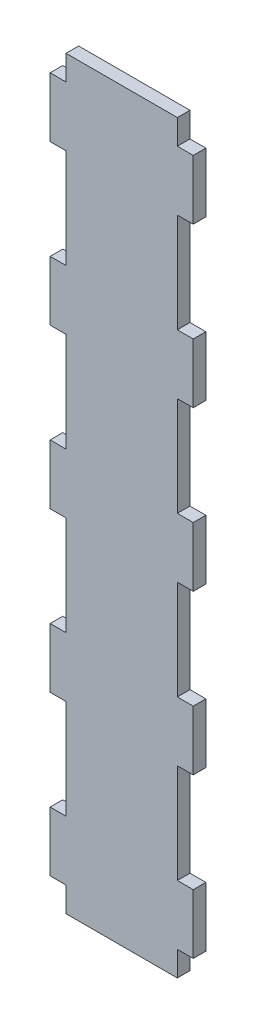
SolidWorks part; units mm, degrees
note: The reader was unsure of these and kept them because the rebuilt part matched: thickness of "Base-Flange1", "Sheet-Metal1", "Sheet-Metal2", "Sheet-Metal3", "Sheet-Metal4".
material "Acrylic (Medium-high impact)"
ref_plane "Front Plane" through (0, 0, 0) normal (0, 0, 1) x (1, 0, 0)
ref_plane "Top Plane" through (0, 0, 0) normal (0, 1, 0) x (1, 0, 0)
ref_plane "Right Plane" through (0, 0, 0) normal (1, 0, 0) x (0, 0, -1)
sketch "Sketch1" plane through (0, 0, 0) normal (0, 0, 1) x (1, 0, 0)
  line L1 (7.0811, 110.7088) -> (43.0811, 110.7088)
  line L2 (7.0811, 110.7088) -> (7.0811, -89.2912)
  line L3 (7.0811, -89.2912) -> (43.0811, -89.2912)
  line L4 (43.0811, 110.7088) -> (43.0811, -89.2912)
  dimension "D1" = 36
  dimension "D2" = 200
base flange "Base-Flange1" sketch "Sketch1" thickness 3.175 reverse thickness direction no parameters "D1"=0.7366
sketch "Sketch2" plane through (0, 0, 0) normal (0, 0, 1) x (1, 0, 0)
  line L0 (7.0811, 110.7088) -> (7.0811, -89.2912) construction
  line L1 (7.0811, -101.7912) -> (11.0811, -101.7912)
  line L2 (7.0811, -101.7912) -> (7.0811, -76.7912)
  line L3 (7.0811, -76.7912) -> (11.0811, -76.7912)
  line L4 (11.0811, -101.7912) -> (11.0811, -76.7912)
  line L6 (25.0811, -89.2912) -> (25.0811, -51.7912) construction
  line L7 (39.0811, -101.7912) -> (39.0811, -76.7912)
  line L8 (43.0811, -76.7912) -> (39.0811, -76.7912)
  line L9 (43.0811, -101.7912) -> (43.0811, -76.7912)
  line L10 (43.0811, -101.7912) -> (39.0811, -101.7912)
  line L11 (7.0811, -89.2912) -> (43.0811, -89.2912) construction
  dimension "D1" = 4
  dimension "D2" = 25
  dimension "D3" = 12.5
extrude "Cut-Extrude1" cut sketch "Sketch2" against normal blind 10
pattern_linear "LPattern1" count 6 spacing 40 along (0, 1, 0) of "Cut-Extrude1"
sketch "Sketch3" plane through (0, 0, 0) normal (0, 0, 1) x (1, 0, 0)
  line L0 (11.0811, 98.2088) -> (11.0811, 110.7088) construction
  line L1 (11.0811, 104.4588) -> (39.0811, 104.4588)
  line L2 (11.0811, 104.4588) -> (11.0811, 110.7088)
  line L3 (11.0811, 110.7088) -> (39.0811, 110.7088)
  line L4 (39.0811, 104.4588) -> (39.0811, 110.7088)
  line L5 (11.0811, -76.7912) -> (11.0811, -89.2912) construction
  line L6 (11.0811, -83.0412) -> (39.0811, -83.0412)
  line L7 (11.0811, -83.0412) -> (11.0811, -89.2912)
  line L8 (11.0811, -89.2912) -> (39.0811, -89.2912)
  line L9 (39.0811, -83.0412) -> (39.0811, -89.2912)
extrude "Cut-Extrude2" cut sketch "Sketch3" against normal blind 10
sketch "Bend-Lines1" [suppressed] plane through (0, 0, 0) normal (0, 1, 0) x (1, 0, 0)
sketch "Bounding-Box1" [suppressed] plane through (0, 0, 0) normal (0, 1, 0) x (1, 0, 0)
sheet metal parameters "Sheet-Metal1" thickness 3.175 parameters "D1"=0.7366, "D7"=0.7366
flat pattern "Flat-Pattern1" [suppressed]
sketch "Bend-Lines2" plane through (0, 0, 0) normal (0, 1, 0) x (1, 0, 0)
sketch3d "Bounding-Box2" [suppressed]
  line L0 (44.2561, 110.7088, 0) -> (44.2561, -89.2912, 0) construction
  line L1 (4.2561, 110.7088, 0) -> (4.2561, -89.2912, 0) construction
  line L2 (44.2561, 110.7088, 0) -> (4.2561, 110.7088, 0) construction
  line L3 (44.2561, -89.2912, 0) -> (4.2561, -89.2912, 0) construction
sheet metal parameters "Sheet-Metal2" thickness 3.175 parameters "D1"=0.7366, "D7"=0.7366
flat pattern "Flat-Pattern1"
sketch "Bend-Lines2" plane through (0, 0, 0) normal (0, 1, 0) x (1, 0, 0)
sketch3d "Bounding-Box2" [suppressed]
  line L0 (44.2561, 110.7088, 0) -> (44.2561, -89.2912, 0) construction
  line L1 (4.2561, 110.7088, 0) -> (4.2561, -89.2912, 0) construction
  line L2 (44.2561, 110.7088, 0) -> (4.2561, 110.7088, 0) construction
  line L3 (44.2561, -89.2912, 0) -> (4.2561, -89.2912, 0) construction
sheet metal parameters "Sheet-Metal3" thickness 3.175 parameters "D1"=0.7366, "D7"=0.7366
flat pattern "Flat-Pattern1"
sketch "Bend-Lines2" plane through (0, 0, 0) normal (0, 1, 0) x (1, 0, 0)
sketch3d "Bounding-Box2" [suppressed]
  line L0 (43.0811, 110.7088, 0) -> (43.0811, -89.2912, 0) construction
  line L1 (7.0811, 110.7088, 0) -> (7.0811, -89.2912, 0) construction
  line L2 (43.0811, 110.7088, 0) -> (7.0811, 110.7088, 0) construction
  line L3 (43.0811, -89.2912, 0) -> (7.0811, -89.2912, 0) construction
sheet metal parameters "Sheet-Metal4" thickness 3.175 parameters "D1"=0.7366, "D7"=0.7366
flat pattern "Flat-Pattern1"
sketch "Bend-Lines2" plane through (0, 0, 0) normal (0, 1, 0) x (1, 0, 0)
sketch3d "Bounding-Box2" [suppressed]
  line L0 (43.0811, 104.4588, 0) -> (43.0811, -83.0412, 0) construction
  line L1 (7.0811, 104.4588, 0) -> (7.0811, -83.0412, 0) construction
  line L2 (43.0811, 104.4588, 0) -> (7.0811, 104.4588, 0) construction
  line L3 (43.0811, -83.0412, 0) -> (7.0811, -83.0412, 0) construction
